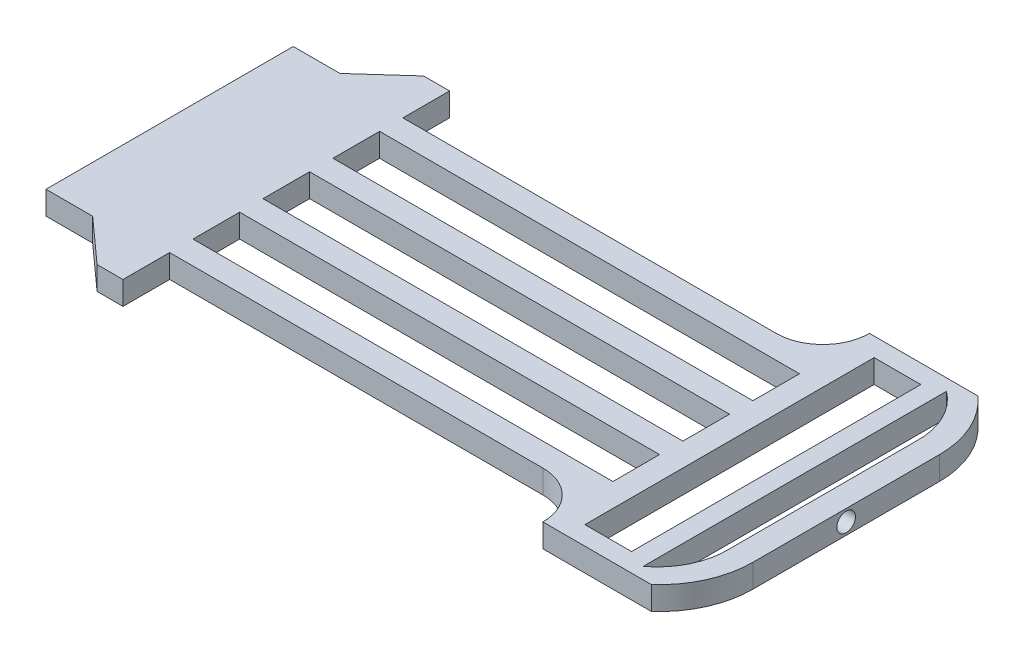
SolidWorks part; units mm, degrees
ref_plane "Ön Düzlem" through (0, 0, 0) normal (0, 0, 1) x (1, 0, 0)
ref_plane "Üst Düzlem" through (0, 0, 0) normal (0, 1, 0) x (1, 0, 0)
ref_plane "Sağ Düzlem" through (0, 0, 0) normal (1, 0, 0) x (0, 0, -1)
sketch "Çizim1" plane through (0, 0, 0) normal (0, 1, 0) x (1, 0, 0)
  line L0 (0, 0) -> (0, 53)
  line L1 (0, 53) -> (15, 53)
  line L2 (15, 53) -> (30, 66.5)
  line L3 (30, 66.5) -> (150, 66.5)
  line L4 (150, 66.5) -> (150, -13.5)
  line L5 (150, -13.5) -> (30, -13.5)
  line L6 (30, -13.5) -> (15, 0)
  line L7 (15, 0) -> (0, 0)
  line L8 (0, 26.5) -> (214.08, 26.5) construction
  dimension "D1" = 53
  dimension "D2" = 150
  dimension "D3" = 15
  dimension "D4" = 15
  dimension "D5" = 80
  dimension "D6" = 15
extrude "Yükseklik-Ekstrüzyon1" add sketch "Çizim1" along normal blind 7
sketch "Çizim2" plane through (0, 7, 0) normal (0, 1, 0) x (1, 0, 0)
  line L0 (2.5, 53) -> (2.5, -2.7433) construction
  line L1 (15, 53) -> (0, 53) construction
  line L2 (0, 53) -> (0, 0) construction
  line L3 (0, 26.5) -> (35.1734, 26.5) construction
  circle A0 centre (2.5, 41.25) radius 1.5
  circle A1 centre (2.5, 11.75) radius 1.5
  dimension "D2" = 3
  dimension "D3" = 3
  dimension "D1" = 2.5
  dimension "D4" = 29.5
extrude "Kes-Ekstrüzyon1" cut sketch "Çizim2" against normal blind 7
chamfer "Pah1" distance 2.5 angle 45 2 edges at (2.5, 7, -10.25) (2.5, 7, -39.75)
sketch "Çizim3" plane through (0, 0, 13.5) normal (0, 0, 1) x (1, 0, 0)
  line L0 (30, 3.5) -> (160.3071, 3.5) construction
  line L1 (30, 7) -> (30, 0) construction
  line L2 (0, 7) -> (0, 0) construction
  circle A0 centre (46.24, 3.5) radius 2
  dimension "D1" = 4
  dimension "D2" = 46.24
extrude "Kes-Ekstrüzyon2" cut sketch "Çizim3" against normal blind 10
sketch "Çizim4" plane through (0, 0, -66.5) normal (0, 0, -1) x (-1, 0, 0)
  line L0 (-30, 3.5) -> (-173.4144, 3.5) construction
  line L1 (-30, 7) -> (-30, 0) construction
  line L2 (0, 7) -> (0, 0) construction
  circle A0 centre (-46.24, 3.5) radius 2
  point P8 (0, 3.5)
  dimension "D1" = 4
  dimension "D2" = 46.24
extrude "Kes-Ekstrüzyon3" cut sketch "Çizim4" against normal blind 10
fillet "Radyus1" radius 20 2 edges at (150, 3.5, 13.5) (150, 3.5, -66.5)
sketch "Çizim5" plane through (0, 7, 0) normal (0, 1, 0) x (1, 0, 0)
  line L0 (30, -13.5) -> (30, 82.5573) construction
  line L1 (30, -8.5) -> (120, -8.5)
  line L2 (30, -8.5) -> (30, 1.5)
  line L3 (30, 1.5) -> (120, 1.5)
  line L4 (120, -8.5) -> (120, 1.5)
  line L5 (30, 21.5) -> (120, 21.5)
  line L6 (30, 21.5) -> (30, 31.5)
  line L7 (30, 31.5) -> (120, 31.5)
  line L8 (120, 21.5) -> (120, 31.5)
  line L9 (30, 36.5) -> (120, 36.5)
  line L10 (30, 36.5) -> (30, 46.5)
  line L11 (30, 46.5) -> (120, 46.5)
  line L12 (120, 36.5) -> (120, 46.5)
  line L13 (30, 51.5) -> (120, 51.5)
  line L14 (30, 51.5) -> (30, 61.5)
  line L15 (30, 61.5) -> (120, 61.5)
  line L16 (120, 51.5) -> (120, 61.5)
  line L17 (30, -13.5) -> (130, -13.5) construction
  line L18 (130, 66.5) -> (30, 66.5) construction
  line L20 (120, 16.5) -> (30, 16.5)
  line L21 (120, 16.5) -> (120, 6.5)
  line L22 (120, 6.5) -> (30, 6.5)
  line L23 (30, 16.5) -> (30, 6.5)
  line L25 (125, -8.5) -> (135, -8.5)
  line L26 (125, -8.5) -> (125, 61.5)
  line L27 (125, 61.5) -> (135, 61.5)
  line L28 (135, -8.5) -> (135, 61.5)
  dimension "D1" = 10
  dimension "D2" = 10
  dimension "D3" = 10
  dimension "D4" = 10
  dimension "D5" = 5
  dimension "D6" = 5
  dimension "D7" = 90
  dimension "D8" = 5
  dimension "D9" = 5
  dimension "D10" = 10
  dimension "D11" = 5
  dimension "D12" = 5
  dimension "D13" = 10
extrude "Kes-Ekstrüzyon4" cut sketch "Çizim5" against normal blind 10
fillet "Radyus2" radius 4 2 edges at (135, 3.5, -61.5) (135, 3.5, 8.5)
sketch "Çizim6" plane through (0, 7, 0) normal (0, 1, 0) x (1, 0, 0)
  line L0 (139, -6) -> (139, 59)
  line L1 (145, 6.5) -> (145, 46.5)
  line L3 (150, 6.5) -> (150, 46.5) construction
  line L4 (135, -4.5) -> (135, 57.5) construction
  line L5 (150, 26.5) -> (128.177, 26.5) construction
  arc A0 (139, -6) -> (145, 6.5) centre (130.0081, 6.0061) ccw
  arc A1 (145, 46.5) -> (139, 59) centre (130.0081, 46.9939) ccw
  dimension "D4" = 15
  dimension "D5" = 15
  dimension "D1" = 5
  dimension "D2" = 4
  dimension "D3" = 65
extrude "Kes-Ekstrüzyon5" cut sketch "Çizim6" against normal blind 10
sketch "Çizim8" plane through (0, 7, 0) normal (0, 1, 0) x (1, 0, 0)
  line L0 (15, 53) -> (0, 53) construction
  line L1 (0, 0) -> (5, 0)
  line L2 (0, 0) -> (0, 53)
  line L3 (0, 53) -> (5, 53)
  line L4 (5, 0) -> (5, 53)
  dimension "D1" = 5
extrude "Kes-Ekstrüzyon6" cut sketch "Çizim8" against normal blind 10
sketch "Çizim9" plane through (5, 0, 0) normal (-1, 0, 0) x (0, 0, 1)
  line L0 (0, 7) -> (-8.6275, 7) construction
  line L1 (-8.0682, 7) -> (-16.7926, 7)
  line L2 (-8.0682, 7) -> (-8.0682, 4.8214)
  line L3 (-8.0682, 4.8214) -> (-16.7926, 4.8214)
  line L4 (-16.7926, 7) -> (-16.7926, 4.8214)
  line L5 (-14.8725, 7) -> (-38.1275, 7) construction
  line L6 (-36.665, 7) -> (-45.8293, 7)
  line L7 (-36.665, 7) -> (-36.665, 4.8214)
  line L8 (-36.665, 4.8214) -> (-45.8293, 4.8214)
  line L9 (-45.8293, 7) -> (-45.8293, 4.8214)
extrude "Yükseklik-Ekstrüzyon2" add sketch "Çizim9" against normal blind 10
sketch "Çizim10" plane through (0, 7, 0) normal (0, 1, 0) x (1, 0, 0)
  line L0 (5, 26.5) -> (159.8449, 26.5) construction
  line L1 (15, -18.5) -> (155, -18.5)
  line L2 (15, -18.5) -> (15, -8.5)
  line L3 (15, -8.5) -> (155, -8.5)
  line L4 (155, -18.5) -> (155, -8.5)
  line L5 (15, 71.5) -> (155, 71.5)
  line L6 (15, 71.5) -> (15, 61.5)
  line L7 (15, 61.5) -> (155, 61.5)
  line L8 (155, 71.5) -> (155, 61.5)
  line L9 (5, 0) -> (5, 53) construction
  dimension "D1" = 70
  dimension "D2" = 10
  dimension "D3" = 10
  dimension "D4" = 140
  dimension "D5" = 140
  dimension "D6" = 10
extrude "Kes-Ekstrüzyon7" cut sketch "Çizim10" against normal blind 10
sketch "Çizim11" plane through (0, 7, 0) normal (0, 1, 0) x (1, 0, 0)
  line L1 (125, -8.5) -> (135, -8.5)
  line L2 (125, -8.5) -> (125, -4.5)
  line L3 (125, -4.5) -> (135, -4.5)
  line L4 (135, -8.5) -> (135, -4.5)
  line L5 (125, 61.5) -> (135, 61.5)
  line L6 (125, 61.5) -> (125, 57.5)
  line L7 (125, 57.5) -> (135, 57.5)
  line L8 (135, 61.5) -> (135, 57.5)
extrude "Yükseklik-Ekstrüzyon3" add sketch "Çizim11" against normal up to vertex (7 mm away) up to point (131, 0, -61.5)
fillet "Radyus3" radius 10 2 edges at (120, 3.5, -1.5) (120, 3.5, -51.5)
sketch "Çizim12" plane through (0, 7, 0) normal (0, 1, 0) x (1, 0, 0)
  line L0 (5, 0) -> (5, 53) construction
  line L1 (5, 11.5) -> (9, 11.5)
  line L2 (5, 11.5) -> (5, 18.5)
  line L3 (5, 18.5) -> (9, 18.5)
  line L4 (9, 11.5) -> (9, 18.5)
  line L5 (5, 26.5) -> (25.7605, 26.5) construction
  line L7 (5, 34.5) -> (9, 34.5)
  line L8 (5, 34.5) -> (5, 41.5)
  line L9 (5, 41.5) -> (9, 41.5)
  line L10 (9, 34.5) -> (9, 41.5)
  dimension "D1" = 7
  dimension "D2" = 7
  dimension "D3" = 30
  dimension "D4" = 4
extrude "Yükseklik-Ekstrüzyon4" add sketch "Çizim12" along normal blind 7
fillet "Radyus4" radius 5 4 edges at (7, 7, -11.5) (7, 7, -18.5) (7, 7, -34.5) (7, 7, -41.5)
sketch "Çizim13" plane through (5, 0, 0) normal (-1, 0, 0) x (0, 0, 1)
  line L0 (-38, 14) -> (-38, 0) construction
  line L1 (-41.5, 14) -> (-34.5, 14) construction
  line L2 (-53, 0) -> (0, 0) construction
  line L3 (-15, 14) -> (-15, 0) construction
  line L4 (-18.5, 14) -> (-11.5, 14) construction
  circle A0 centre (-38, 10.5) radius 1.5
  circle A1 centre (-15, 10.5) radius 1.5
  dimension "D1" = 3
  dimension "D2" = 3
  dimension "D3" = 3.5
  dimension "D4" = 3.5
extrude "Kes-Ekstrüzyon8" cut sketch "Çizim13" against normal blind 7
chamfer "Pah2" distance 1.5 angle 45 2 edges at (9, 10.5, -13.5) (9, 10.5, -36.5)
fillet "Radyus5" radius 2 4 edges at (7, 14, -41.5) (7, 14, -34.5) (7, 14, -11.5) (7, 14, -18.5)
sketch "Çizim14" plane through (0, 7, 0) normal (0, 1, 0) x (1, 0, 0)
  line L0 (9, 16.5) -> (9, 18.5) construction
  line L1 (153.5359, 61.5) -> (9, 61.5)
  line L2 (153.5359, 61.5) -> (153.5359, -8.5)
  line L3 (153.5359, -8.5) -> (9, -8.5)
  line L4 (9, 61.5) -> (9, -8.5)
  line L5 (30, -8.5) -> (24.4444, -8.5) construction
  line L6 (24.4444, 61.5) -> (30, 61.5) construction
extrude "Kes-Ekstrüzyon9" cut sketch "Çizim14" against normal blind 2
fillet "Radyus6" radius 2 2 edges at (7, 7, -53) (7, 7, 0)
sketch "Çizim16" plane through (150, 0, 0) normal (1, 0, 0) x (0, 0, -1)
  line L0 (6.5, 2.5) -> (46.5, 2.5) construction
  line L1 (6.5, 5) -> (6.5, 0) construction
  line L2 (46.5, 0) -> (46.5, 5) construction
  line L3 (26.5, 5) -> (26.5, 0) construction
  line L4 (53, 5) -> (0, 5) construction
  line L5 (6.5, 0) -> (46.5, 0) construction
  circle A0 centre (26.5, 2.5) radius 2
  dimension "D1" = 4
extrude "Kes-Ekstrüzyon11" cut sketch "Çizim16" against normal blind 7
sketch "Çizim17" plane through (9, 0, 0) normal (1, 0, 0) x (0, 0, -1)
  line L6 (0, 5) -> (53, 5)
  line L7 (51, 7) -> (46.5, 7)
  line L8 (39.5, 14) -> (36.5, 14)
  line L9 (29.5, 7) -> (23.5, 7)
  line L10 (16.5, 14) -> (13.5, 14)
  line L11 (6.5, 7) -> (2, 7)
  line L12 (0, 5) -> (53, 5)
  line L13 (51, 7) -> (46.5, 7)
  line L14 (39.5, 14) -> (36.5, 14)
  line L15 (29.5, 7) -> (23.5, 7)
  line L16 (16.5, 14) -> (13.5, 14)
  line L17 (6.5, 7) -> (2, 7)
  arc A10 (53, 5) -> (51, 7) centre (51, 5) ccw
  arc A11 (41.5, 12) -> (46.5, 7) centre (46.5, 12) ccw
  arc A12 (41.5, 12) -> (39.5, 14) centre (39.5, 12) ccw
  arc A13 (36.5, 14) -> (34.5, 12) centre (36.5, 12) ccw
  arc A14 (29.5, 7) -> (34.5, 12) centre (29.5, 12) ccw
  arc A15 (18.5, 12) -> (23.5, 7) centre (23.5, 12) ccw
  arc A16 (18.5, 12) -> (16.5, 14) centre (16.5, 12) ccw
  arc A17 (13.5, 14) -> (11.5, 12) centre (13.5, 12) ccw
  arc A18 (6.5, 7) -> (11.5, 12) centre (6.5, 12) ccw
  arc A19 (2, 7) -> (0, 5) centre (2, 5) ccw
  arc A20 (53, 5) -> (51, 7) centre (51, 5) ccw
  arc A21 (41.5, 12) -> (46.5, 7) centre (46.5, 12) ccw
  arc A22 (41.5, 12) -> (39.5, 14) centre (39.5, 12) ccw
  arc A23 (36.5, 14) -> (34.5, 12) centre (36.5, 12) ccw
  arc A24 (29.5, 7) -> (34.5, 12) centre (29.5, 12) ccw
  arc A25 (18.5, 12) -> (23.5, 7) centre (23.5, 12) ccw
  arc A26 (18.5, 12) -> (16.5, 14) centre (16.5, 12) ccw
  arc A27 (13.5, 14) -> (11.5, 12) centre (13.5, 12) ccw
  arc A28 (6.5, 7) -> (11.5, 12) centre (6.5, 12) ccw
  arc A29 (2, 7) -> (0, 5) centre (2, 5) ccw
  dimension "D1" = 0
extrude "Kes-Ekstrüzyon12" cut sketch "Çizim17" against normal blind 10 body kept at (5, 5, 0)
